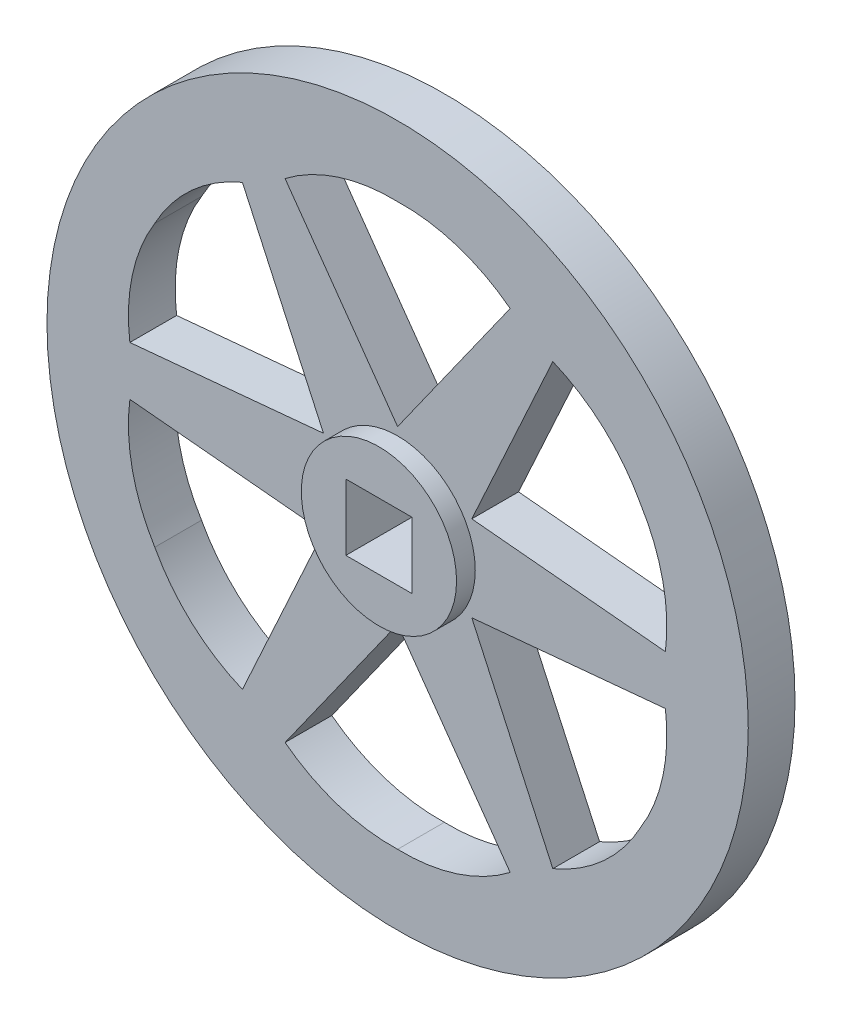
SolidWorks part; units mm, degrees
ref_plane "Front Plane" through (0, 0, 0) normal (0, 0, 1) x (1, 0, 0)
ref_plane "Top Plane" through (0, 0, 0) normal (0, 1, 0) x (1, 0, 0)
ref_plane "Right Plane" through (0, 0, 0) normal (1, 0, 0) x (0, 0, -1)
sketch "Sketch1" plane through (0, 0, 0) normal (0, 0, 1) x (1, 0, 0)
  line L1 (3.5355, -3.5355) -> (-3.5355, -3.5355)
  line L2 (3.5355, -3.5355) -> (3.5355, 3.5355)
  line L3 (3.5355, 3.5355) -> (-3.5355, 3.5355)
  line L4 (-3.5355, -3.5355) -> (-3.5355, 3.5355)
  line L5 (3.5355, -3.5355) -> (-3.5355, 3.5355) construction
  line L6 (3.5355, 3.5355) -> (-3.5355, -3.5355) construction
  circle A0 centre (0, 0) radius 37.5
  circle A1 centre (0, 0) radius 5 construction
  dimension "D1" = 75
  dimension "D2" = 10
extrude "Boss-Extrude1" add sketch "Sketch1" along normal mid plane 5
sketch "Sketch2" plane through (0, 0, 0) normal (0, 0, 1) x (1, 0, 0)
  line L0 (0, 0) -> (0, 32.5712) construction
  line L1 (0, 9.1586) -> (-12.0371, 26.1152)
  line L2 (0, 9.1586) -> (12.0371, 26.1152)
  arc A0 (-12.0371, 26.1152) -> (0, 29.9881) centre (-0.5568, 11.0765) cw
  arc A1 (12.0371, 26.1152) -> (0, 29.9881) centre (0.5568, 11.0765) ccw
extrude "Cut-Extrude1" cut sketch "Sketch2" along normal mid plane 8
pattern_circular "CirPattern1" count 6 over 360 about axis through (0, 0, 2.5) along (0, 0, -1) of "Cut-Extrude1" reverse direction yes
sketch "Sketch4" plane through (0, 0, 2.5) normal (0, 0, 1) x (1, 0, 0)
  line L1 (3.5355, -3.5355) -> (-3.5355, -3.5355)
  line L2 (3.5355, -3.5355) -> (3.5355, 3.5355)
  line L3 (3.5355, 3.5355) -> (-3.5355, 3.5355)
  line L4 (-3.5355, -3.5355) -> (-3.5355, 3.5355)
  line L5 (3.5355, -3.5355) -> (-3.5355, 3.5355) construction
  line L6 (3.5355, 3.5355) -> (-3.5355, -3.5355) construction
  circle A0 centre (0, 0) radius 8.3027
  circle A1 centre (0, 0) radius 5 construction
extrude "Boss-Extrude2" add sketch "Sketch4" along normal blind 2
